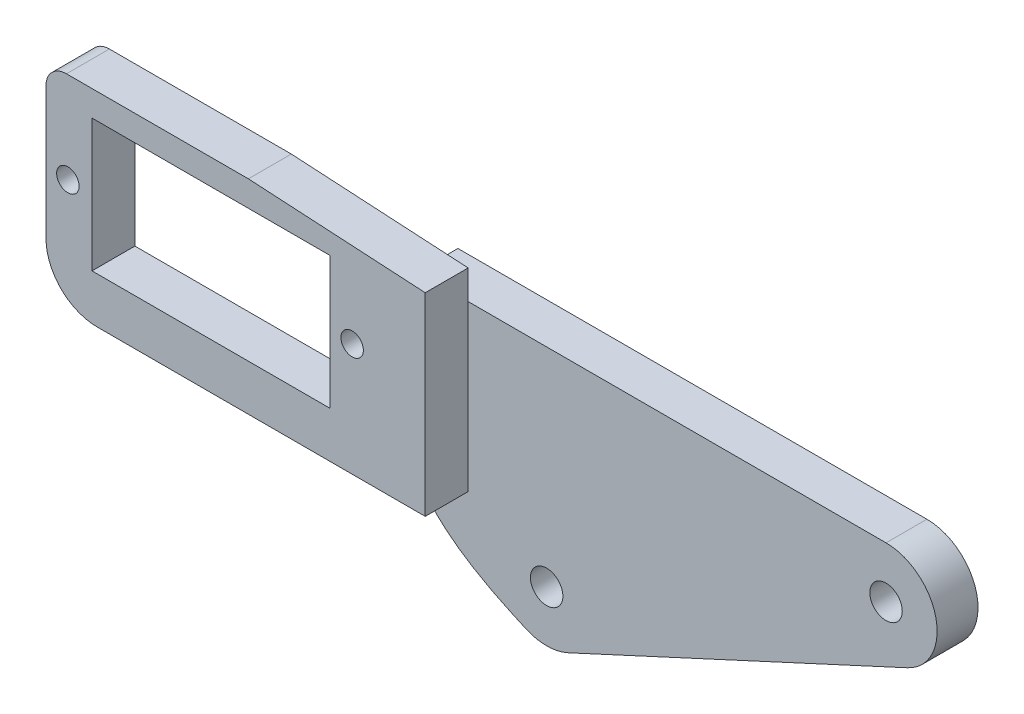
SolidWorks part; units mm, degrees
note: '?' marks a value the reader was unsure of.
ref_plane "Front Plane" through (0, 0, 0) normal (0, 0, 1) x (1, 0, 0)
ref_plane "Top Plane" through (0, 0, 0) normal (0, 1, 0) x (1, 0, 0)
ref_plane "Right Plane" through (0, 0, 0) normal (1, 0, 0) x (0, 0, -1)
sketch "Sketch1" plane through (0, 0, 0) normal (0, 0, 1) x (1, 0, 0)
  line L3 (-33.54, 5) -> (33.54, 5)
  line L4 (-1.7232, -19.885) -> (-35.6013, -4.5553)
  line L5 (2.434, -19.8692) -> (35.6359, -4.5395)
  arc A3 (-33.54, 5) -> (-35.6013, -4.5553) centre (-33.54, 0) ccw
  arc A4 (33.54, 5) -> (35.6359, -4.5395) centre (33.54, 0) cw
  arc A5 (-1.7232, -19.885) -> (2.434, -19.8692) centre (0.3381, -15.3297) ccw
  point P0 (-33.54, 0)
  point P1 (33.54, 0)
  point P3 (0.3381, -15.3297)
  point P16 (0, 5)
  dimension "D4" = 5
  dimension "D1" = 67.08
  dimension "D2" = 37.185
  dimension "D3" = 36.57
extrude "Boss-Extrude1" add sketch "Sketch1" along normal blind 2.5 and the other way blind 1.5
sketch "Sketch2" plane through (0, 0, 2.5) normal (0, 0, 1) x (1, 0, 0)
  circle A0 centre (-33.54, 0) radius 1.5875
  circle A1 centre (33.54, 0) radius 1.5875
  circle A2 centre (0.3381, -15.3297) radius 1.5875
  dimension "D1" = 3.175
extrude "Cut-Extrude1" cut sketch "Sketch2" against normal through all
ref_axis "Axis2" through (-33.54, 0, -1.5) along (0, 0, 1)?
ref_plane "Plane2" through (-33.54, 0, 0) normal (1, 0, 0) x (0, 0, -1)
ref_plane "Plane3" through (-16.04, 0, 0) normal (-1, 0, 0) x (0, 0, 1)
sketch "Sketch5" plane through (0, 0, -1.5) normal (0, 0, -1) x (-1, 0, 0)
  circle A0 centre (33.54, 0) radius 1.5875 construction
  circle A1 centre (33.54, 0) radius 1.5875
sketch "Sketch3" plane through (-16.04, 0, 0) normal (-1, 0, 0) x (0, 0, 1)
  line L0 (-1.5, -4.5553) -> (-1.5, -19.885) construction
  line L5 (-1.5, -19.885) -> (2.5, -19.885) construction
  line L6 (2.5, -19.885) -> (2.5, -4.5553) construction
  line L7 (-1.5, 5) -> (-1.5, -4.5553) construction
  line L8 (2.5, -4.5553) -> (2.5, 5) construction
  line L9 (2.5, 5) -> (-1.5, 5) construction
  line L10 (-1.5, -4.5553) -> (-1.5, -19.885)
  line L11 (-1.5, -19.885) -> (2.5, -19.885)
  line L12 (2.5, -19.885) -> (2.5, -4.5553)
  line L13 (-1.5, 5) -> (-1.5, -4.5553)
  line L14 (2.5, -4.5553) -> (2.5, 5)
  line L15 (2.5, 5) -> (-1.5, 5)
extrude "Cut-Extrude3" cut sketch "Sketch3" along normal through all
ref_plane "Plane4" through (-12.34, 0, 0) normal (-1, 0, 0) x (0, 0, 1)
sketch "Sketch4" plane through (-12.34, 0, 0) normal (-1, 0, 0) x (0, 0, 1)
  line L0 (2.5, -13.4067) -> (2.5, 5) construction
  line L5 (2.5, -13.4067) -> (2.5, 5) construction
  line L6 (2.5, 5) -> (6.7, 5) construction
  line L7 (2.5, -11.1) -> (6.7, -11.1)
  line L8 (2.5, -11.1) -> (2.5, 11.1)
  line L9 (2.5, 11.1) -> (6.7, 11.1)
  line L10 (6.7, -11.1) -> (6.7, 11.1)
  dimension "D1" = 4.2
  dimension "D2" = 6.1
  dimension "D3" = 16.1
extrude "Boss-Extrude2" add sketch "Sketch4" along normal blind 32.1
sketch "Sketch6" plane through (0, 0, 2.5) normal (0, 0, -1) x (-1, 0, 0)
  line L0 (44.44, 11.1) -> (12.34, 11.1) construction
  line L1 (39.94, 6.35) -> (16.64, 6.35)
  line L2 (39.94, 6.35) -> (39.94, -6.6)
  line L3 (39.94, -6.6) -> (16.64, -6.6)
  line L4 (16.64, 6.35) -> (16.64, -6.6)
  line L5 (44.44, -11.1) -> (16.04, -11.1) construction
  line L6 (44.44, 11.1) -> (44.44, -11.1) construction
  line L8 (12.34, 11.1) -> (12.34, 5) construction
  dimension "D1" = 4.75
  dimension "D2" = 4.5
  dimension "D3" = 4.5
  dimension "D4" = 4.3
extrude "Cut-Extrude4" cut sketch "Sketch6" against normal up to surface (4.2 mm away) up to face at (-28.39, 0, 6.7)
sketch "Sketch7" plane through (-12.34, 0, 0) normal (1, 0, 0) x (0, 0, -1)
  line L1 (-6.7, -11.1) -> (-2.5, -11.1)
  line L2 (-6.7, -11.1) -> (-6.7, 11.1)
  line L3 (-6.7, 11.1) -> (-2.5, 11.1)
  line L4 (-2.5, -11.1) -> (-2.5, 11.1)
extrude "Boss-Extrude3" add sketch "Sketch7" along normal blind 5
sketch "Sketch8" plane through (-12.34, 0, 0) normal (-1, 0, 0) x (0, 0, 1)
  line L17 (-1.5, -13.4067) -> (2.5, -13.4067)
  line L18 (2.5, -13.4067) -> (2.5, -11.1)
  line L19 (2.5, -11.1) -> (2.5, 5)
  line L20 (2.5, 5) -> (-1.5, 5)
  line L21 (-1.5, 5) -> (-1.5, -13.4067)
  line L23 (2.5, -13.4067) -> (2.5, -11.1)
  line L24 (2.5, -11.1) -> (2.5, 5)
  line L25 (2.5, 5) -> (-1.5, 5)
  line L26 (-1.5, 5) -> (-1.5, -13.4067)
  line L30 (2.5, -13.4067) -> (-1.5, -13.4067)
  line L31 (-1.5, -13.4067) -> (-1.5, -19.885)
  line L32 (-1.5, -19.885) -> (2.5, -19.885)
  line L33 (2.5, -19.885) -> (2.5, -13.4067)
  line L35 (-1.5, -13.4067) -> (-1.5, -19.885)
  line L36 (-1.5, -19.885) -> (2.5, -19.885)
  line L37 (2.5, -19.885) -> (2.5, -13.4067)
  dimension "D1" = 0
  dimension "D2" = 0
extrude "Cut-Extrude5" cut sketch "Sketch8" along normal up to surface (3.7 mm away) up to face at (-16.04, -5.5827, 0.9)
fillet "Fillet1" radius 5 1 edges at (-44.44, -11.1, 4.6)
fillet "Fillet2" radius 13 1 edges at (-12.34, -15.081, 0.5)
hole_wizard "Ø2.0mm Dowel Hole1" positions "Sketch9" profile "Sketch10" hole size "Ø2.0" standard "ANSI Metric"
sketch "Sketch9" plane through (0, 0, 6.7) normal (0, 0, 1) x (1, 0, 0)
  line L0 (-44.44, -6.1) -> (-44.44, 11.1) construction
  line L1 (-16.64, -6.6) -> (-16.64, 6.35) construction
  line L2 (-44.44, 11.1) -> (-7.34, 11.1) construction
  point P0 (-42.3, -0.06)
  point P2 (-14.49, -0.06)
  dimension "D1" = 2.14
  dimension "D2" = 2.15
  dimension "D3" = 11.16
sketch "Sketch10" plane through (-42.3, -0.06, 6.7) normal (1, 0, 0) x (0, -1, 0)
  line L0 (0, 0) -> (0, 4.8599)
  line L1 (0, 4.8599) -> (1.1, 4.199)
  line L2 (1.1, 4.199) -> (1.1, 0)
  line L5 (1.1, 0) -> (0, 0)
  line L10 (0, 4.8599) -> (-1.1, 4.199) construction
  line L11 (0, -6.35) -> (0, 107.95) construction
  dimension "Hole Dia." = 2.2
  dimension "Hole Depth" = 4.199
  dimension "Drill Angle" = 118
sketch "Sketch12" plane through (0, 0, 6.7) normal (0, 0, 1) x (1, 0, 0)
  line L0 (-44.44, -6.1) -> (-44.44, 11.1) construction
  line L1 (-44.44, 8.85) -> (-7.34, 8.85)
  line L2 (-44.44, 8.85) -> (-44.44, 11.1)
  line L3 (-44.44, 11.1) -> (-7.34, 11.1)
  line L4 (-7.34, 8.85) -> (-7.34, 11.1)
  dimension "D1" = 2.25
extrude "Cut-Extrude6" cut sketch "Sketch12" along direction (0, 0, 1) on the side against the normal up to next (4.2 mm away)
fillet "Fillet3" radius 2 1 edges at (-44.44, 8.85, 4.6)
sketch "Sketch13" plane through (0, 0, 6.7) normal (0, 0, 1) x (1, 0, 0)
  line L0 (-7.34, 8.85) -> (-7.34, 7.85)
  line L1 (-7.34, 8.85) -> (-7.34, -11.1) construction
  line L2 (-7.34, 7.85) -> (-24.64, 8.85)
  line L3 (-42.44, 8.85) -> (-7.34, 8.85) construction
  line L4 (-24.64, 8.85) -> (-7.34, 8.85)
  dimension "D1" = 8
  dimension "D2" = 1
extrude "Cut-Extrude7" cut sketch "Sketch13" against normal up to next
